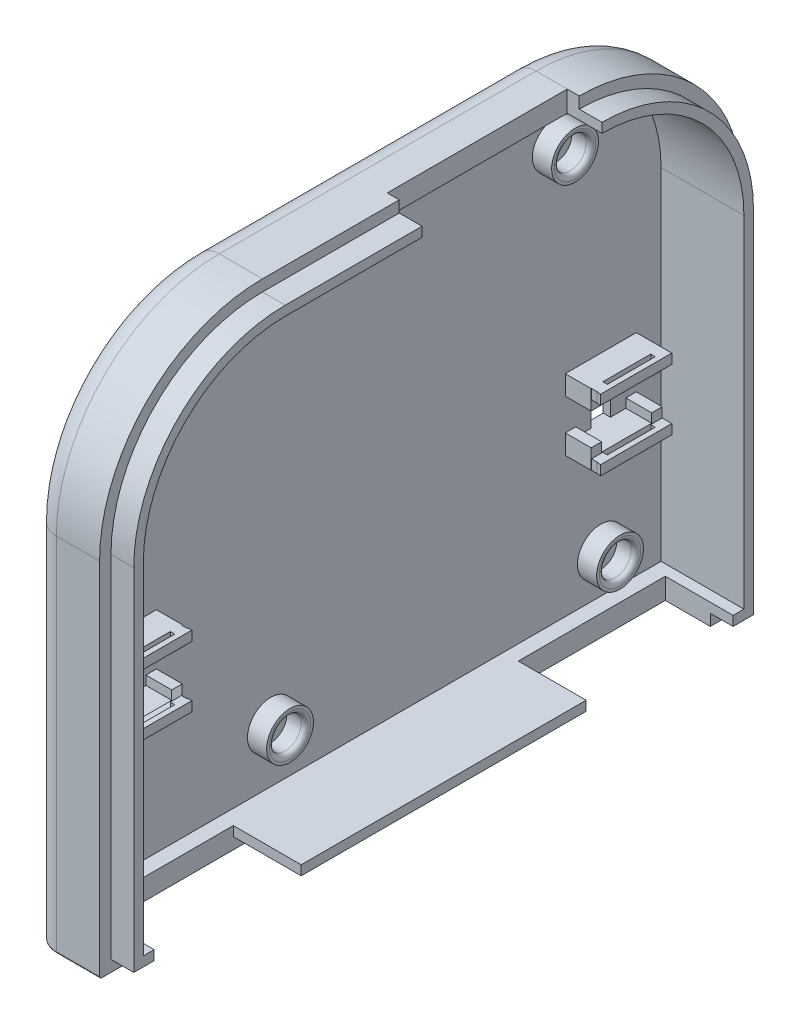
SolidWorks part; units mm, degrees
ref_plane "Front Plane" through (0, 0, 0) normal (0, 0, 1) x (1, 0, 0)
ref_plane "Top Plane" through (0, 0, 0) normal (0, 1, 0) x (1, 0, 0)
ref_plane "Right Plane" through (0, 0, 0) normal (1, 0, 0) x (0, 0, -1)
sketch "Sketch1" plane through (0, 0, 0) normal (1, 0, 0) x (0, 0, -1)
  line L0 (-52.8, 99.65) -> (52.8, 99.65)
  line L1 (-107.1, 45.35) -> (-107.1, -45.35)
  line L2 (-70, -75.35) -> (70, -75.35)
  line L3 (107.1, 45.35) -> (107.1, -45.35)
  line L4 (107.1, 0) -> (-107.1, 0) construction
  line L5 (0, 99.65) -> (0, -75.35) construction
  line L11 (107.1, -45.35) -> (107.1, -75.35)
  line L12 (107.1, -75.35) -> (70, -75.35)
  line L13 (-83.2, -1.7) -> (-76.8, -1.7)
  line L14 (-83.2, -1.7) -> (-83.2, -18.3)
  line L15 (-83.2, -18.3) -> (-76.8, -18.3)
  line L16 (-76.8, -1.7) -> (-76.8, -18.3)
  line L17 (-83.2, -1.7) -> (-76.8, -18.3) construction
  line L18 (-83.2, -18.3) -> (-76.8, -1.7) construction
  line L19 (76.8, -1.7) -> (83.2, -1.7)
  line L20 (76.8, -1.7) -> (76.8, -18.3)
  line L21 (76.8, -18.3) -> (83.2, -18.3)
  line L22 (83.2, -1.7) -> (83.2, -18.3)
  line L23 (76.8, -1.7) -> (83.2, -18.3) construction
  line L24 (76.8, -18.3) -> (83.2, -1.7) construction
  line L25 (80, -10) -> (-80, -10) construction
  line L27 (-107.1, -45.35) -> (-107.1, -75.35)
  line L28 (-107.1, -75.35) -> (-70, -75.35)
  arc A0 (52.8, 99.65) -> (107.1, 45.35) centre (52.8, 45.35) cw
  arc A1 (-52.8, 99.65) -> (-107.1, 45.35) centre (-52.8, 45.35) ccw
  point P16 (0, 0)
  point P17 (-80, -10)
  point P32 (80, -10)
  point P39 (-80, -10)
  point P40 (0, -10)
  dimension "D4" = 54.3
  dimension "D2" = 175
  dimension "D3" = 214.2
  dimension "D5" = 140
  dimension "D6" = 30
  dimension "D7" = 160
  dimension "D8" = 6.4
  dimension "D9" = 16.6
  dimension "D10" = 6.4
  dimension "D11" = 16.6
  dimension "D12" = 10
extrude "Boss-Extrude1" add sketch "Sketch1" along normal blind 2.4 contours L2 L3 A0 L0 A1 L1 L19 L22 L21 L20 L13 L16 L15 L14 region at (0, 9.6317, 0)
sketch "Sketch9" plane through (2.4, 0, 0) normal (1, 0, 0) x (0, 0, -1)
  line L17 (52.8, 99.65) -> (-52.8, 99.65)
  line L31 (52.8, 99.65) -> (-52.8, 99.65)
  line L32 (-107.1, 45.35) -> (-107.1, -75.35)
  line L33 (-107.1, 45.35) -> (-107.1, -75.35)
  line L34 (-107.1, -75.35) -> (107.1, -75.35)
  line L39 (107.1, -75.35) -> (107.1, 45.35)
  line L43 (107.1, -75.35) -> (107.1, 45.35)
  line L45 (-107.1, -75.35) -> (107.1, -75.35)
  arc A15 (-52.8, 99.65) -> (-107.1, 45.35) centre (-52.8, 45.35) ccw
  arc A16 (-52.8, 99.65) -> (-107.1, 45.35) centre (-52.8, 45.35) ccw
  arc A17 (107.1, 45.35) -> (52.8, 99.65) centre (52.8, 45.35) ccw
  arc A18 (107.1, 45.35) -> (52.8, 99.65) centre (52.8, 45.35) ccw
  dimension "D1" = 0
sketch "Sketch10" plane through (2.4, 0, 0) normal (1, 0, 0) x (0, 0, -1)
  line L0 (65, -55.35) -> (0, -55.35) construction
  line L1 (-65, -55.35) -> (65, -55.35) construction
  line L2 (-65, -55.35) -> (-65, 54.65) construction
  line L3 (-65, 54.65) -> (65, 54.65) construction
  line L4 (65, -55.35) -> (65, 54.65) construction
  line L5 (-65, -55.35) -> (65, 54.65) construction
  line L6 (-65, 54.65) -> (65, -55.35) construction
  line L7 (0, -55.35) -> (-65, -55.35) construction
  line L8 (-107.1, -75.35) -> (107.1, -75.35) construction
  line L9 (0, -0.35) -> (0, 0) construction
  line L10 (0, -0.35) -> (0, -50.35) construction
  line L11 (-65, 54.65) -> (-65, 70.65) construction
  line L12 (-65, 70.65) -> (-70, 70.65) construction
  line L13 (0, -50.35) -> (-30, -50.35) construction
  circle A11 centre (-30, -50.35) radius 2.3
  circle A13 centre (65, 69.65) radius 2.3
  circle A14 centre (80, -55.35) radius 2.3
  circle A15 centre (-70, 70.65) radius 2.3
  point P0 (0, -0.35)
  point P8 (29.0003, -50.35)
  point P11 (0, -55.35)
  point P12 (32.5, -55.35)
  point P14 (-32.5, -55.35)
  point P15 (-42.5255, -50.35)
  dimension "D3" = 15
  dimension "D4" = 20
  dimension "D8" = 4.6
  dimension "D1" = 130
  dimension "D2" = 110
  dimension "D5" = 50
  dimension "D6" = 15
  dimension "D7" = 16
  dimension "D9" = 5
  dimension "D10" = 30
extrude "Cut-Extrude1" cut sketch "Sketch10" against normal blind 100 and the other way blind 1000
sketch "Sketch12" plane through (2.4, 0, 0) normal (1, 0, 0) x (0, 0, -1)
  line L5 (-88.35, -18.3) -> (-88.35, -15.3)
  line L6 (-88.35, -18.3) -> (-88.35, -1.7) construction
  line L22 (71.65, -18.3) -> (71.65, -15.3)
  line L23 (71.65, -18.3) -> (71.65, -1.7) construction
  line L24 (71.65, -18.3) -> (88.35, -18.3) construction
  line L25 (88.35, -18.3) -> (88.35, -1.7) construction
  line L26 (71.65, -1.7) -> (88.35, -1.7) construction
  line L27 (71.65, -18.3) -> (88.35, -1.7) construction
  line L28 (88.35, -18.3) -> (71.65, -1.7) construction
  line L29 (71.65, -1.7) -> (71.65, -4.7)
  line L30 (88.35, -18.3) -> (88.35, -15.3)
  line L31 (88.35, -1.7) -> (88.35, -4.7)
  line L32 (71.65, -1.7) -> (88.35, -1.7)
  line L33 (88.35, -18.3) -> (71.65, -18.3)
  line L34 (88.35, -15.3) -> (91.85, -15.3)
  line L35 (71.65, -15.3) -> (68.15, -15.3)
  line L36 (68.15, -15.3) -> (68.15, -21.8)
  line L37 (68.15, -21.8) -> (91.85, -21.8)
  line L38 (91.85, -21.8) -> (91.85, -15.3)
  line L39 (71.65, -4.7) -> (68.15, -4.7)
  line L40 (68.15, -4.7) -> (68.15, 1.8)
  line L41 (68.15, 1.8) -> (91.85, 1.8)
  line L42 (91.85, 1.8) -> (91.85, -4.7)
  line L43 (91.85, -4.7) -> (88.35, -4.7)
  line L44 (83.2, -18.3) -> (76.8, -1.7) construction
  line L45 (83.2, -1.7) -> (76.8, -18.3) construction
  line L46 (-88.35, -18.3) -> (-71.65, -18.3) construction
  line L47 (-71.65, -18.3) -> (-71.65, -1.7) construction
  line L48 (-88.35, -1.7) -> (-71.65, -1.7) construction
  line L49 (-88.35, -18.3) -> (-71.65, -1.7) construction
  line L50 (-71.65, -18.3) -> (-88.35, -1.7) construction
  line L51 (-88.35, -1.7) -> (-88.35, -4.7)
  line L52 (-71.65, -18.3) -> (-71.65, -15.3)
  line L53 (-71.65, -1.7) -> (-71.65, -4.7)
  line L54 (-88.35, -1.7) -> (-71.65, -1.7)
  line L55 (-71.65, -18.3) -> (-88.35, -18.3)
  line L56 (-71.65, -15.3) -> (-68.15, -15.3)
  line L57 (-88.35, -15.3) -> (-91.85, -15.3)
  line L58 (-91.85, -15.3) -> (-91.85, -21.8)
  line L59 (-91.85, -21.8) -> (-68.15, -21.8)
  line L60 (-68.15, -21.8) -> (-68.15, -15.3)
  line L61 (-88.35, -4.7) -> (-91.85, -4.7)
  line L62 (-91.85, -4.7) -> (-91.85, 1.8)
  line L63 (-91.85, 1.8) -> (-68.15, 1.8)
  line L64 (-68.15, 1.8) -> (-68.15, -4.7)
  line L65 (-68.15, -4.7) -> (-71.65, -4.7)
  line L66 (-76.8, -18.3) -> (-83.2, -1.7) construction
  line L67 (-83.2, -18.3) -> (-76.8, -1.7) construction
  point P3 (-0.1438, 64.1533)
  point P4 (-80, -10)
  point P19 (80, -10)
  point P21 (-80, -10)
  point P30 (380.6447, 32.9453)
  point P31 (130.7088, -20.4974)
  point P32 (80, -10)
  point P49 (169.9078, -49.5925)
  dimension "D3" = 16.7
  dimension "D4" = 16.6
  dimension "D5" = 10.6
  dimension "D6" = 3.5
  dimension "D7" = 3.5
  dimension "D8" = 3.5
  dimension "D9" = 3.5
  dimension "D10" = 4.9497
  dimension "D11" = 16.7
  dimension "D12" = 16.6
  dimension "D13" = 10.6
  dimension "D14" = 3.5
  dimension "D15" = 3.5
  dimension "D16" = 3.5
  dimension "D17" = 3.5
  dimension "D18" = 4.9497
  dimension "D19" = 4.9497
  dimension "D20" = 7.3824
  dimension "D21" = 23.5468
  dimension "D22" = 24.088
  dimension "D23" = 4.9497
  dimension "D24" = 7.3824
  dimension "D25" = 23.5468
  dimension "D26" = 24.088
extrude "Boss-Extrude2" add sketch "Sketch12" along normal blind 8.6
sketch "Sketch14" plane through (11, 0, 0) normal (1, 0, 0) x (0, 0, -1)
  line L0 (-91.85, 1.8) -> (-91.85, -4.7) construction
  line L1 (-91.85, 1.8) -> (-68.15, 1.8)
  line L2 (-91.85, 1.8) -> (-91.85, -1.45)
  line L3 (-91.85, -1.45) -> (-68.15, -1.45)
  line L4 (-68.15, 1.8) -> (-68.15, -1.45)
  line L5 (-68.15, 1.8) -> (-91.85, 1.8) construction
  line L6 (-68.15, -4.7) -> (-68.15, 1.8) construction
  line L7 (-68.15, -21.8) -> (-68.15, -15.3) construction
  line L8 (-91.85, -21.8) -> (-68.15, -21.8)
  line L9 (-91.85, -21.8) -> (-91.85, -18.55)
  line L10 (-91.85, -18.55) -> (-68.15, -18.55)
  line L11 (-68.15, -21.8) -> (-68.15, -18.55)
  line L12 (91.85, -21.8) -> (91.85, -15.3) construction
  line L13 (68.15, -21.8) -> (91.85, -21.8)
  line L14 (68.15, -21.8) -> (68.15, -18.55)
  line L15 (68.15, -18.55) -> (91.85, -18.55)
  line L16 (91.85, -21.8) -> (91.85, -18.55)
  line L17 (91.85, -4.7) -> (91.85, 1.8) construction
  line L18 (68.15, 1.8) -> (91.85, 1.8)
  line L19 (68.15, 1.8) -> (68.15, -1.45)
  line L20 (68.15, -1.45) -> (91.85, -1.45)
  line L21 (91.85, 1.8) -> (91.85, -1.45)
extrude "Boss-Extrude3" add sketch "Sketch14" along normal blind 3.2
sketch "Sketch16" plane through (0, -1.45, 0) normal (0, -1, 0) x (1, 0, 0)
  line L0 (11, 91.85) -> (11, 68.15) construction
  line L1 (11, 68.3952) -> (12.9651, 68.3952)
  line L2 (11, 68.3952) -> (11, 51.6632)
  line L3 (11, 51.6632) -> (12.9651, 51.6632)
  line L4 (12.9651, 68.3952) -> (12.9651, 51.6632)
  line L5 (11, -68.15) -> (11, -91.85) construction
  line L6 (11, -51.6659) -> (12.9651, -51.6659)
  line L7 (11, -51.6659) -> (11, -68.2634)
  line L8 (11, -68.2634) -> (12.9651, -68.2634)
  line L9 (12.9651, -51.6659) -> (12.9651, -68.2634)
extrude "Cut-Extrude2" cut sketch "Sketch16" against normal blind 100 and the other way blind 100
sketch "Sketch17" plane through (0, 0, 0) normal (1, 0, 0) x (0, 0, -1)
  line L0 (-103.9, 45.35) -> (-103.9, -72.15) construction
  line L1 (-103.9, -72.15) -> (103.9, -72.15) construction
  line L2 (103.9, -72.15) -> (103.9, 45.35) construction
  line L3 (52.8, 96.45) -> (-52.8, 96.45) construction
  line L4 (52.8, 99.65) -> (-52.8, 99.65)
  line L5 (-107.1, 45.35) -> (-107.1, -75.35)
  line L6 (-107.1, -75.35) -> (107.1, -75.35)
  line L7 (107.1, -75.35) -> (107.1, 45.35)
  line L8 (52.8, 99.65) -> (-52.8, 99.65) construction
  line L9 (-107.1, 45.35) -> (-107.1, -75.35) construction
  line L11 (107.1, -75.35) -> (107.1, 45.35) construction
  line L16 (100.1, -68.35) -> (100.1, 45.35)
  line L17 (52.8, 92.65) -> (-52.8, 92.65)
  line L18 (-100.1, 45.35) -> (-100.1, -68.35)
  line L19 (-100.1, -68.35) -> (100.1, -68.35)
  line L24 (52.8, 95.85) -> (-52.8, 95.85)
  line L25 (-103.3, 45.35) -> (-103.3, -71.55)
  line L27 (103.3, -71.55) -> (103.3, 45.35)
  line L28 (-107.1, -75.35) -> (107.1, -75.35) construction
  line L29 (-103.3, -71.55) -> (103.3, -71.55) construction
  line L31 (-103.3, -71.55) -> (103.3, -71.55)
  arc A0 (103.9, 45.35) -> (52.8, 96.45) centre (52.8, 45.35) ccw construction
  arc A1 (-52.8, 96.45) -> (-103.9, 45.35) centre (-52.8, 45.35) ccw construction
  arc A2 (-52.8, 99.65) -> (-107.1, 45.35) centre (-52.8, 45.35) ccw
  arc A3 (107.1, 45.35) -> (52.8, 99.65) centre (52.8, 45.35) ccw
  arc A4 (-52.8, 99.65) -> (-107.1, 45.35) centre (-52.8, 45.35) ccw construction
  arc A5 (107.1, 45.35) -> (52.8, 99.65) centre (52.8, 45.35) ccw construction
  arc A8 (100.1, 45.35) -> (52.8, 92.65) centre (52.8, 45.35) ccw
  arc A9 (-52.8, 92.65) -> (-100.1, 45.35) centre (-52.8, 45.35) ccw
  arc A12 (-52.8, 95.85) -> (-103.3, 45.35) centre (-52.8, 45.35) ccw
  arc A13 (103.3, 45.35) -> (52.8, 95.85) centre (52.8, 45.35) ccw
  dimension "D4" = 167.4
  dimension "D5" = 206.6
  dimension "D7" = 207.8
  dimension "D8" = 214.2
  dimension "D9" = 3.2
  dimension "D2" = 3.2
  dimension "D10" = 3.2
  dimension "D11" = 3.2
  dimension "D1" = 0
  dimension "D3" = 3.2
  dimension "D6" = 0.6
extrude "Boss-Extrude4" add sketch "Sketch17" along normal blind 30
sketch "Sketch21" plane through (2.4, 0, 0) normal (1, 0, 0) x (0, 0, -1)
  line L4 (-107.1, -75.35) -> (107.1, -75.35)
  line L6 (-107.1, -75.35) -> (107.1, -75.35)
  line L8 (52.8, 99.65) -> (-52.8, 99.65)
  line L9 (-107.1, 45.35) -> (-107.1, -75.35)
  line L11 (107.1, -75.35) -> (107.1, 45.35)
  line L12 (52.8, 99.65) -> (-52.8, 99.65)
  line L13 (-107.1, 45.35) -> (-107.1, -75.35)
  line L15 (107.1, -75.35) -> (107.1, 45.35)
  arc A4 (-52.8, 99.65) -> (-107.1, 45.35) centre (-52.8, 45.35) ccw
  arc A5 (107.1, 45.35) -> (52.8, 99.65) centre (52.8, 45.35) ccw
  arc A6 (-52.8, 99.65) -> (-107.1, 45.35) centre (-52.8, 45.35) ccw
  arc A7 (107.1, 45.35) -> (52.8, 99.65) centre (52.8, 45.35) ccw
  dimension "D1" = 0
sketch "Sketch22" plane through (2.4, 0, 0) normal (1, 0, 0) x (0, 0, -1)
  line L0 (-107.1, -75.35) -> (107.1, -75.35) construction
  line L1 (-107.1, -75.35) -> (107.1, -75.35)
  line L21 (52.8, 99.65) -> (-52.8, 99.65)
  line L22 (107.1, -75.35) -> (107.1, 45.35)
  line L24 (-107.1, 45.35) -> (-107.1, -75.35)
  line L25 (52.8, 99.65) -> (-52.8, 99.65)
  line L26 (107.1, -75.35) -> (107.1, 45.35)
  line L28 (-107.1, 45.35) -> (-107.1, -75.35)
  line L44 (-103.3, -71.55) -> (103.3, -71.55)
  line L45 (103.3, -71.55) -> (103.3, 45.35)
  line L46 (52.8, 95.85) -> (-52.8, 95.85)
  line L47 (-103.3, 45.35) -> (-103.3, -71.55)
  line L48 (-103.3, -71.55) -> (103.3, -71.55)
  line L49 (103.3, -71.55) -> (103.3, 45.35)
  line L50 (52.8, 95.85) -> (-52.8, 95.85)
  line L51 (-103.3, 45.35) -> (-103.3, -71.55)
  arc A6 (-52.8, 99.65) -> (-107.1, 45.35) centre (-52.8, 45.35) ccw
  arc A7 (107.1, 45.35) -> (52.8, 99.65) centre (52.8, 45.35) ccw
  arc A8 (-52.8, 99.65) -> (-107.1, 45.35) centre (-52.8, 45.35) ccw
  arc A9 (107.1, 45.35) -> (52.8, 99.65) centre (52.8, 45.35) ccw
  arc A20 (103.3, 45.35) -> (52.8, 95.85) centre (52.8, 45.35) ccw
  arc A21 (-52.8, 95.85) -> (-103.3, 45.35) centre (-52.8, 45.35) ccw
  arc A22 (103.3, 45.35) -> (52.8, 95.85) centre (52.8, 45.35) ccw
  arc A23 (-52.8, 95.85) -> (-103.3, 45.35) centre (-52.8, 45.35) ccw
  dimension "D1" = 0
  dimension "D2" = 0
extrude "Boss-Extrude7" add sketch "Sketch22" along normal blind 20
sketch "Sketch23" plane through (0, -75.35, 0) normal (0, -1, 0) x (1, 0, 0)
  line L0 (0, 99.1) -> (0, 107.1)
  line L1 (0, 107.1) -> (8, 107.1)
  line L2 (8, -107.1) -> (0, -107.1)
  line L3 (0, -107.1) -> (0, -99.1)
  line L8 (0, 107.1) -> (0, -107.1)
  line L9 (0, -107.1) -> (22.4, -107.1)
  line L10 (22.4, -107.1) -> (22.4, 107.1)
  line L11 (22.4, 107.1) -> (0, 107.1)
  line L12 (0, 99.1) -> (0, -99.1) construction
  line L13 (8, -107.1) -> (22.4, -107.1) construction
  line L15 (22.4, 107.1) -> (8, 107.1) construction
  arc A0 (0, 99.1) -> (8, 107.1) centre (8, 99.1) cw
  arc A1 (0, -99.1) -> (8, -107.1) centre (8, -99.1) ccw
  dimension "D2" = 8
  dimension "D1" = 0
extrude "Cut-Extrude4" cut sketch "Sketch23" against normal through all
fillet "Fillet4" radius 8 5 edges at (0, 92.7258, 79.3335) (0, 99.65, 0) (0, 92.7258, -79.3335) (1.5353, 63.957, 103.8124) (1.5353, 63.957, -103.8124)
sketch "Sketch26" plane through (22.4, 0, 0) normal (1, 0, 0) x (0, 0, -1)
  line L1 (-47.5, -68.3365) -> (47.5, -68.3365)
  line L2 (47.5, -68.3365) -> (47.5, -71.55)
  line L6 (47.5, -71.55) -> (-47.5, -71.55)
  line L7 (-47.5, -71.55) -> (-47.5, -68.3365)
  line L8 (-103.3, -71.55) -> (103.3, -71.55) construction
  line L9 (-96.5, -79.5369) -> (96.5, -79.5369)
  line L10 (-96.5, -79.5369) -> (-96.5, -63.5631)
  line L11 (-96.5, -63.5631) -> (96.5, -63.5631)
  line L12 (96.5, -79.5369) -> (96.5, -63.5631)
  line L13 (-96.5, -79.5369) -> (96.5, -63.5631) construction
  line L14 (-96.5, -63.5631) -> (96.5, -79.5369) construction
  line L15 (107.1, -75.35) -> (107.1, 45.35) construction
  point P0 (0, -71.55)
  point P9 (0, -68.3365)
  point P13 (0, -68.3365)
  point P16 (0, -68.3365)
  dimension "D1" = 10.6
  dimension "D2" = 15.9739
  dimension "D3" = 95
  dimension "D4" = 3.2135
extrude "Cut-Extrude7" cut sketch "Sketch26" against normal blind 15 and the other way blind 20
sketch "Sketch28" plane through (0, 99.65, 0) normal (0, 1, 0) x (1, 0, 0)
  line L0 (22.4, 52.8) -> (18.4, 52.8)
  line L1 (22.4, 52.8) -> (8, 52.8) construction
  line L2 (18.4, 52.8) -> (18.4, -7.2)
  line L3 (18.4, -7.2) -> (53.1003, -7.2)
  line L4 (53.1003, -7.2) -> (53.1003, 52.8)
  line L5 (53.1003, 52.8) -> (22.4, 52.8)
  dimension "D1" = 4
  dimension "D2" = 60
extrude "Cut-Extrude8" cut sketch "Sketch28" against normal blind 10
sketch "Sketch29" plane through (0, -1.45, 0) normal (0, -1, 0) x (1, 0, 0)
  line L5 (11, 91.85) -> (11, 68.3952) construction
  line L7 (11, 88.1226) -> (11, 72.1226)
  line L8 (11, 72.1226) -> (12.5, 72.1226)
  line L9 (12.5, 72.1226) -> (12.5, 88.1226)
  line L10 (12.5, 88.1226) -> (11, 88.1226)
  line L12 (11, -68.2634) -> (11, -91.85) construction
  line L13 (11, -72.0567) -> (11, -88.0567)
  line L14 (11, -88.0567) -> (12.5, -88.0567)
  line L15 (12.5, -88.0567) -> (12.5, -72.0567)
  line L16 (12.5, -72.0567) -> (11, -72.0567)
  point P0 (11, 80.1226)
  point P1 (11, -80.0567)
  point P6 (11, 80.1226)
  point P9 (11, -80.0567)
  point P14 (11, -80.0567)
  dimension "D1" = 16
  dimension "D2" = 1.5
  dimension "D3" = 16
  dimension "D4" = 1.5
extrude "Cut-Extrude9" cut sketch "Sketch29" against normal blind 30 and the other way blind 1000
sketch "Sketch30" plane through (2.4, 0, 0) normal (1, 0, 0) x (0, 0, -1)
  circle A0 centre (-70, 70.65) radius 5.3
  circle A1 centre (65, 69.65) radius 5.3
  circle A2 centre (-30, -50.35) radius 5.3
  circle A3 centre (80, -55.35) radius 5.3
  circle A5 centre (65, 69.65) radius 7.8
  circle A6 centre (80, -55.35) radius 7.8
  circle A7 centre (-30, -50.35) radius 7.8
  circle A8 centre (-70, 70.65) radius 7.8
  dimension "D1" = 10.6
  dimension "D2" = 15.6
extrude "Boss-Extrude8" add sketch "Sketch30" along normal blind 6.4
fillet "Fillet7" radius 1.6 4 edges at (8.8, -55.35, -85.3) (8.8, -50.35, 24.7) (8.8, 69.65, -70.3) (8.8, 70.65, 64.7)
fillet "Fillet8" radius 0.8 5 edges at (15.2, -75.35, 107.1) (2.3431, -75.35, 104.7569) (15.2, -75.35, -107.1) (2.3431, -75.35, -104.7569) (0, -75.35, 0)
